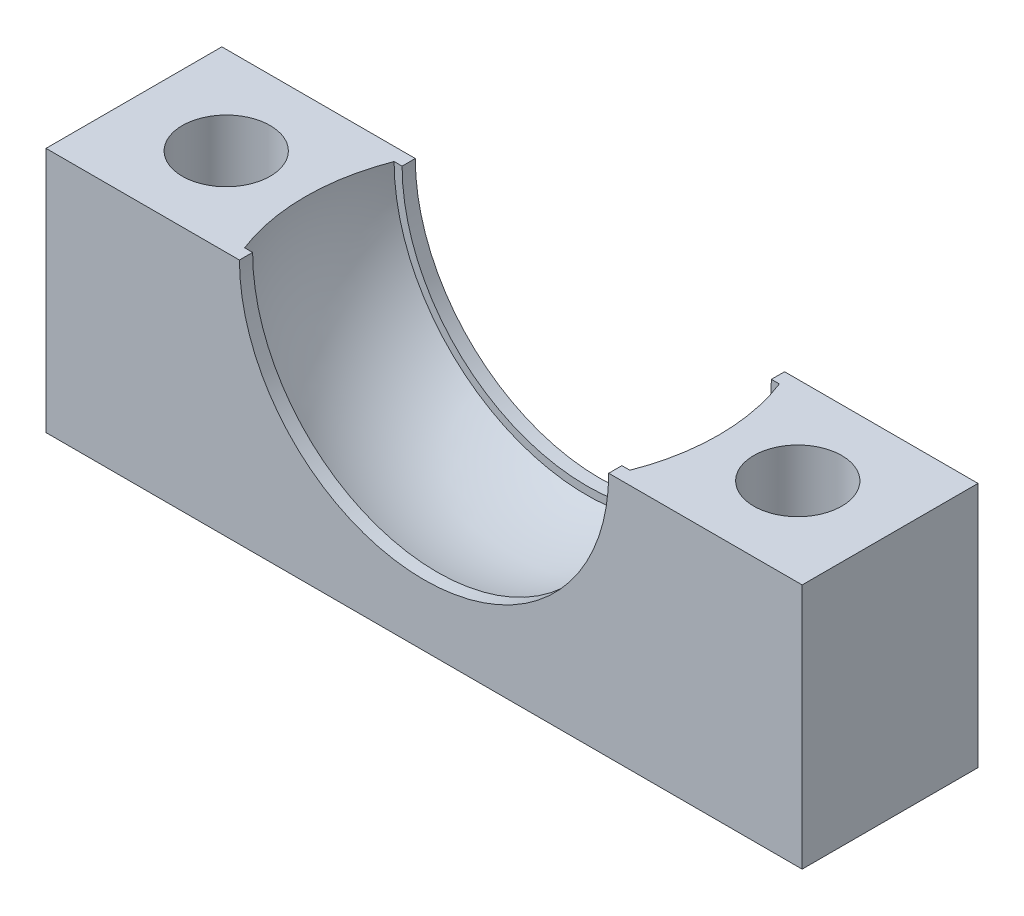
SolidWorks part; units mm, degrees
ref_plane "Front Plane" through (0, 0, 0) normal (0, 0, 1) x (1, 0, 0)
ref_plane "Top Plane" through (0, 0, 0) normal (0, 1, 0) x (1, 0, 0)
ref_plane "Right Plane" through (0, 0, 0) normal (1, 0, 0) x (0, 0, -1)
sketch "Sketch1" plane through (0, 0, 0) normal (0, 0, 1) x (1, 0, 0)
  line L0 (0, 0) -> (0, 79.999) construction
  line L1 (43, 0) -> (-43, 0)
  line L2 (-43, 0) -> (-43, 28)
  line L5 (43, 0) -> (43, 28)
  line L10 (-43, 28) -> (43, 28)
  dimension "D2" = 43
  dimension "D3" = 28
extrude "Boss-Extrude1" add sketch "Sketch1" along normal blind 20
sketch "Sketch2" plane through (0, 0, 0) normal (0, 1, 0) x (1, 0, 0)
  line L1 (-43, -20) -> (-43, 0) construction
  line L2 (-23, -20) -> (-40, -20) construction
  line L3 (0, 0) -> (0, -21.8102) construction
  circle A0 centre (-32.5, -10) radius 5
  circle A1 centre (32.5, -10) radius 5
  point P2 (0, 0)
  point P12 (-43, -10)
  dimension "D1" = 10
  dimension "D2" = 32.5
  dimension "D3" = 10
extrude "Cut-Extrude1" cut sketch "Sketch2" along normal through all
sketch "Sketch4" plane through (0, 28, 0) normal (0, 1, 0) x (-1, 0, 0)
  line L17 (0, 0) -> (0, 20) construction
  line L20 (0, 0) -> (0, 20)
  line L21 (0, 0) -> (21, 0)
  line L22 (0, 20) -> (21, 20)
  line L23 (21, 0) -> (21, 1.5)
  line L24 (21, 1.5) -> (21.9089, 1.5)
  line L25 (0, 10) -> (41.3238, 10) construction
  line L26 (21, 20) -> (21, 18.5)
  line L27 (21, 18.5) -> (21.9089, 18.5)
  arc A2 (21.9089, 18.5) -> (21.9089, 1.5) centre (0, 10) cw
  point P2 (0, 0)
  point P6 (0, 10)
  point P7 (0, 10)
  dimension "D2" = 23.5
  dimension "D1" = 20
  dimension "D3" = 1.5
  dimension "D4" = 21
revolve "Cut-Revolve1" cut sketch "Sketch4" angle 360 about L20
